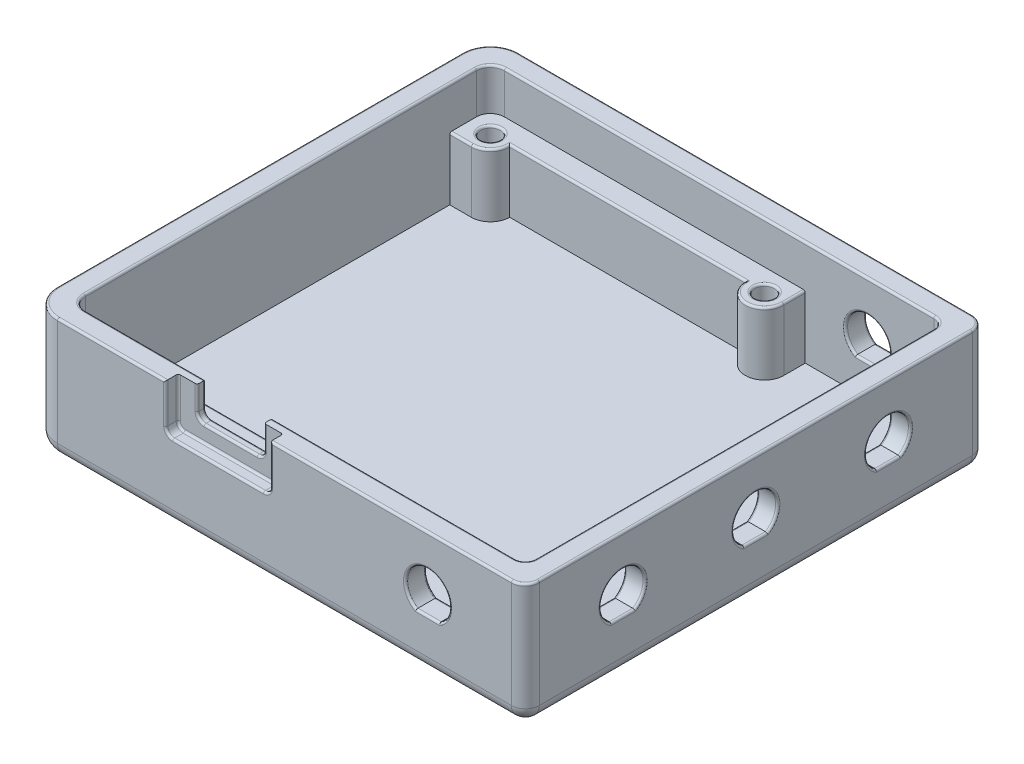
SolidWorks part; units mm, degrees
ref_plane "Front Plane" through (0, 0, 0) normal (0, 0, 1) x (1, 0, 0)
ref_plane "Top Plane" through (0, 0, 0) normal (0, 1, 0) x (1, 0, 0)
ref_plane "Right Plane" through (0, 0, 0) normal (1, 0, 0) x (0, 0, -1)
sketch "Sketch1" plane through (0, 0, 0) normal (0, 1, 0) x (1, 0, 0)
  line L1 (-32.5, 30) -> (32.5, 30)
  line L2 (-32.5, 30) -> (-32.5, -30)
  line L3 (-32.5, -30) -> (32.5, -30)
  line L4 (32.5, 30) -> (32.5, -30)
  line L5 (-32.5, 30) -> (32.5, -30) construction
  line L6 (-32.5, -30) -> (32.5, 30) construction
  line L7 (-35.5, 33) -> (35.5, 33)
  line L8 (-35.5, 33) -> (-35.5, -33)
  line L9 (-35.5, -33) -> (35.5, -33)
  line L10 (35.5, 33) -> (35.5, -33)
  line L11 (-35.5, 33) -> (35.5, -33) construction
  line L12 (-35.5, -33) -> (35.5, 33) construction
  point P0 (0, 0)
  point P6 (0, 0)
  dimension "D1" = 60
  dimension "D2" = 65
  dimension "D3" = 3
  dimension "D4" = 3
extrude "Boss-Extrude1" add sketch "Sketch1" along normal blind 15
sketch "Sketch4" plane through (0, 0, 0) normal (0, -1, 0) x (1, 0, 0)
  line L1 (-35.5, 33) -> (35.5, 33)
  line L2 (-35.5, 33) -> (-35.5, -33)
  line L3 (-35.5, -33) -> (35.5, -33)
  line L4 (35.5, 33) -> (35.5, -33)
extrude "Boss-Extrude3" add sketch "Sketch4" along normal blind 2.5
sketch "Sketch5" plane through (0, 0, 0) normal (0, 1, 0) x (1, 0, 0)
  line L0 (0, 0) -> (-9.7945, 0) construction
  line L6 (-29.42, 26.925) -> (9.831, -26.925) construction
  line L7 (-29.42, -26.925) -> (9.831, 26.925) construction
  line L10 (-29.42, 26.925) -> (9.831, 26.925) construction
  line L11 (-29.42, 26.925) -> (-29.42, -26.925) construction
  line L12 (-29.42, -26.925) -> (9.831, -26.925) construction
  line L13 (9.831, -26.925) -> (9.831, 26.925) construction
  line L14 (-26.67, -26.925) -> (7.081, -26.925)
  line L15 (12.581, -26.925) -> (12.581, -30)
  line L16 (-32.5, -30) -> (32.5, -30) construction
  line L17 (12.581, -30) -> (-32.5, -30)
  line L18 (-32.5, -30) -> (-32.5, -24.175)
  line L19 (-32.5, 30) -> (-32.5, -30) construction
  line L20 (-32.5, -24.175) -> (-29.42, -24.175)
  line L21 (-26.67, 26.925) -> (7.081, 26.925)
  line L22 (-29.42, 24.175) -> (-32.5, 24.175)
  line L23 (-32.5, 24.175) -> (-32.5, 30)
  line L24 (-32.5, 30) -> (12.581, 30)
  line L25 (32.5, 30) -> (-32.5, 30) construction
  line L26 (12.581, 30) -> (12.581, 26.925)
  circle A0 centre (-29.42, 26.925) radius 1.4
  circle A1 centre (9.831, 26.925) radius 1.4
  circle A2 centre (9.831, -26.925) radius 1.4
  circle A3 centre (-29.42, -26.925) radius 1.4
  arc A4 (-29.42, 24.175) -> (-26.67, 26.925) centre (-29.42, 26.925) ccw
  arc A5 (7.081, 26.925) -> (12.581, 26.925) centre (9.831, 26.925) ccw
  arc A6 (12.581, -26.925) -> (7.081, -26.925) centre (9.831, -26.925) ccw
  arc A7 (-26.67, -26.925) -> (-29.42, -24.175) centre (-29.42, -26.925) ccw
  dimension "D3" = 2.8
  dimension "D4" = 2.8
  dimension "D5" = 2.8
  dimension "D6" = 2.8
  dimension "D7" = 5.5
  dimension "D8" = 5.5
  dimension "D9" = 5.5
  dimension "D10" = 5.5
  dimension "D1" = 53.85
  dimension "D2" = 39.251
extrude "Boss-Extrude4" add sketch "Sketch5" along normal blind 9
fillet "Fillet1" radius 2 2 edges at (-32.5, 12, 30) (-32.5, 12, -30)
fillet "Fillet2" radius 4 2 edges at (-35.5, 6.25, -33) (-35.5, 6.25, 33)
fillet "Fillet3" radius 2 8 edges at (2, -2.5, 33) (-34.3284, -2.5, 31.8284) (-35.5, -2.5, 0) (-34.3284, -2.5, -31.8284) (35.5, 6.25, 33) (35.5, -2.5, 0) (35.5, 6.25, -33) (2, -2.5, -33)
sketch "Sketch6" plane through (0, 15, 0) normal (0, 1, 0) x (1, 0, 0)
  line L0 (-32.5, -24.175) -> (-32.5, -28) construction
  line L1 (-13.3, -27.7193) -> (-3.7, -27.7193)
  line L2 (-13.3, -27.7193) -> (-13.3, -35.9519)
  line L3 (-13.3, -35.9519) -> (-3.7, -35.9519)
  line L4 (-3.7, -27.7193) -> (-3.7, -35.9519)
  dimension "D1" = 19.2
  dimension "D2" = 9.6
extrude "Cut-Extrude1" cut sketch "Sketch6" against normal blind 4.45
fillet "Fillet4" radius 1 2 edges at (-3.7, 10.55, 31.5) (-13.3, 10.55, 31.5)
sketch "Sketch7" plane through (0, 0, 33) normal (0, 0, 1) x (1, 0, 0)
  line L0 (-13.3, 13.275) -> (-3.7, 13.275) construction
  line L1 (-16, 18.275) -> (-1, 18.275)
  line L2 (-16, 18.275) -> (-16, 8.275)
  line L3 (-16, 8.275) -> (-1, 8.275)
  line L4 (-1, 18.275) -> (-1, 8.275)
  line L5 (-16, 18.275) -> (-1, 8.275) construction
  line L6 (-16, 8.275) -> (-1, 18.275) construction
  line L7 (-13.3, 11.55) -> (-13.3, 15) construction
  line L8 (-3.7, 15) -> (-3.7, 11.55) construction
  point P0 (-8.5, 13.275)
  dimension "D1" = 15
  dimension "D2" = 10
extrude "Cut-Extrude2" cut sketch "Sketch7" against normal blind 1.8
fillet "Fillet5" radius 1 2 edges at (-1, 8.275, 32.1) (-16, 8.275, 32.1)
sketch "Sketch8" plane through (35.5, 0, 0) normal (1, 0, 0) x (0, 0, -1)
  line L0 (-31, 7.25) -> (31, 7.25) construction
  line L1 (-31, 15) -> (-31, -0.5) construction
  line L2 (31, -0.5) -> (31, 15) construction
  line L3 (-20.6714, 4.58) -> (-17.3286, 4.58)
  line L4 (-19, 10.4) -> (-19, 4.58) construction
  line L5 (-1.6714, 4.58) -> (1.6714, 4.58)
  line L6 (17.3286, 4.58) -> (20.6714, 4.58)
  arc A0 (1.6714, 4.58) -> (-1.6714, 4.58) centre (0, 7.25) ccw
  arc A1 (20.6714, 4.58) -> (17.3286, 4.58) centre (19, 7.25) ccw
  arc A2 (-17.3286, 4.58) -> (-20.6714, 4.58) centre (-19, 7.25) ccw
  dimension "D1" = 6.3
  dimension "D2" = 6.3
  dimension "D3" = 6.3
  dimension "D4" = 12
  dimension "D5" = 12
  dimension "D6" = 5.82
extrude "Cut-Extrude3" cut sketch "Sketch8" against normal up to next
sketch "Sketch9" plane through (0, 0, 33) normal (0, 0, 1) x (1, 0, 0)
  line L0 (33.5, 7.25) -> (21.5, 7.25) construction
  line L1 (33.5, -0.5) -> (33.5, 15) construction
  line L2 (19.8286, 4.58) -> (23.2414, 4.58)
  line L3 (21.5, 10.4) -> (21.535, 4.58) construction
  arc A0 (23.1714, 4.58) -> (19.8286, 4.58) centre (21.5, 7.25) ccw
  dimension "D1" = 6.3
  dimension "D2" = 5.82
  dimension "D3" = 12
extrude "Cut-Extrude4" cut sketch "Sketch9" against normal through all contours L2 A0 region at (21.5, 7.3535, 33)
fillet "Fillet6" radius 0.3 24 edges at (-1, 12.1375, 31.2) (-1.2929, 8.5679, 31.2) (-8.5, 8.275, 31.2) (-15.7071, 8.5679, 31.2) (-3.7, 13.275, 31.2) (-3.9929, 10.8429, 31.2) (-8.5, 10.55, 31.2) (-13.3, 13.275, 31.2) (-1, 12.1375, 33) (-1.2929, 8.5679, 33) (-8.5, 8.275, 33) (-15.7071, 8.5679, 33) (16.25, 15, 33) (34.9142, 15, 32.4142) (35.5, 15, 0) (34.9142, 15, -32.4142) (1, 15, -33) (-34.3284, 15, -31.8284) (-35.5, 15, 0) (-34.3284, 15, 31.8284) (-16, 12.1375, 31.2) (-13.0071, 10.8429, 31.2) (-16, 12.1375, 33) (-23.75, 15, 33)
fillet "Fillet7" radius 1.5 2 edges at (32.5, 7.5, 30) (32.5, 7.5, -30)
fillet "Fillet8" radius 0.3 14 edges at (-13.3, 13.275, 30) (-13.0071, 10.8429, 30) (-8.5, 10.55, 30) (-3.9929, 10.8429, 30) (13.65, 15, 30) (32.0607, 15, 29.5607) (32.5, 15, 0) (32.0607, 15, -29.5607) (-21.9, 15, 30) (-31.9142, 15, 29.4142) (-32.5, 15, 0) (-31.9142, 15, -29.4142) (-3.7, 13.275, 30) (0.25, 15, -30)
fillet "Fillet9" radius 0.3 34 edges at (12.581, 9, 28.4625) (-27.4755, 9, 24.9805) (-30.96, 9, -24.175) (12.581, 9, -28.4625) (9.831, 9, -25.525) (-29.42, 9, -25.525) (-29.42, 9, 28.325) (9.831, 9, 28.325) (9.831, 9, 24.175) (-9.7945, 9, 26.925) (-30.96, 9, 24.175) (-27.4755, 9, -24.9805) (9.831, 9, -24.175) (-9.7945, 9, -26.925) (21.5, 4.58, -30) (21.5, 10.4, -30) (32.5, 4.58, -19) (32.5, 10.4, -19) (32.5, 4.58, 0) (32.5, 10.4, 0) (32.5, 4.58, 19) (32.5, 10.4, 19) (21.5, 4.58, 30) (21.5, 10.4, 30) (21.5, 4.58, 33) (21.5, 10.4, 33) (21.5, 4.58, -33) (21.5, 10.4, -33) (35.5, 4.58, 19) (35.5, 10.4, 19) (35.5, 4.58, 0) (35.5, 10.4, 0) (35.5, 10.4, -19) (35.5, 4.58, -19)
